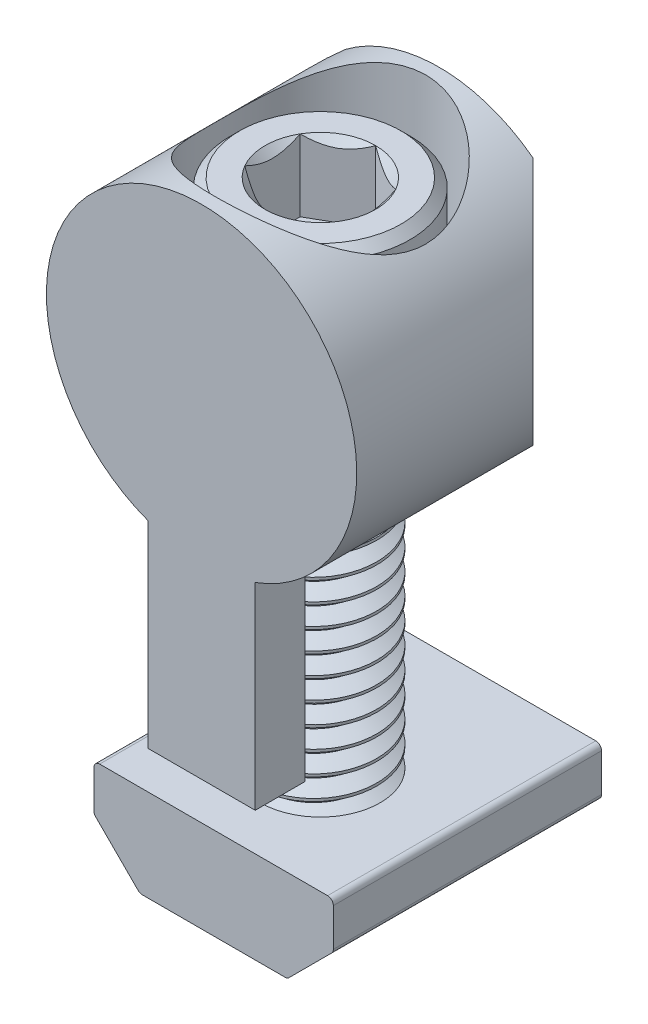
SolidWorks part; units mm, degrees
ref_plane "Front Plane" through (0, 0, 0) normal (0, 0, 1) x (1, 0, 0)
ref_plane "Top Plane" through (0, 0, 0) normal (0, 1, 0) x (1, 0, 0)
ref_plane "Right Plane" through (0, 0, 0) normal (1, 0, 0) x (0, 0, -1)
sketch "Sketch1" plane through (0, 0, 0) normal (0, 1, 0) x (1, 0, 0)
  circle A0 centre (0, 0) radius 3.9688
  point P3 (-3.9688, 0)
  dimension "D1" = 7.9375
extrude "Boss-Extrude1" add sketch "Sketch1" against normal blind 33.02
sketch "Sketch2" plane through (0, -33.02, 0) normal (0, -1, 0) x (1, 0, 0)
  circle A1 centre (0, 0) radius 3.9688
  circle A2 centre (0, 0) radius 3.9688
  point P0 (0, -3.9688)
  dimension "D1" = 0
curve "Helix/Spiral1" pitch 1.4111 height 34.4311 turns 24.4
sketch "Sketch3" plane through (0, 0, 0) normal (1, 0, 0) x (0, 0, -1)
  line L0 (4.1215, -32.9318) -> (2.8994, -33.6374) construction
  line L1 (2.8994, -33.6374) -> (4.1215, -34.3429) construction
  line L2 (4.1215, -34.3429) -> (4.1215, -32.9318) construction
  line L3 (3.0522, -33.5492) -> (3.0522, -33.7256) construction
  line L4 (3.9688, -33.02) -> (3.9688, -34.2547) construction
  line L5 (2.8994, -33.6374) -> (3.0522, -33.6374) construction
  line L6 (3.9688, -33.6374) -> (4.1215, -33.6374) construction
  line L8 (2.8994, -33.6374) -> (-3.9688, -33.6374) construction
  line L9 (3.0522, -33.5492) -> (4.0451, -32.9759)
  line L10 (3.0522, -33.5492) -> (3.0522, -33.7256)
  line L11 (3.0522, -33.7256) -> (4.0451, -34.2988)
  line L12 (4.0451, -34.2988) -> (4.0451, -32.9759)
  line L14 (-3.9688, -33.6374) -> (-3.9688, -32.2263) construction
  line L15 (-3.9688, -32.2263) -> (-3.9688, -30.8151) construction
  line L16 (-3.9688, -30.8151) -> (-3.9688, -29.404) construction
  line L17 (-3.9688, -29.404) -> (-3.9687, -27.9929) construction
  line L18 (-3.9688, 0) -> (-3.9688, -33.02) construction
  point P15 (4.0451, -33.6374)
  dimension "D1" = 1.4111
  dimension "D2" = 0.1764
sweep "Cut-Sweep1" cut profiles "Sketch3" path "Helix/Spiral1" align with end faces yes
sketch "Sketch4" plane through (0, -33.02, 0) normal (0, -1, 0) x (1, 0, 0)
  circle A0 centre (0, 0) radius 2.8994
extrude "Cut-Extrude1" cut sketch "Sketch4" against normal blind 1.4111 draft 45 flip side to cut
sketch "Sketch5" plane through (0, 0, 0) normal (0, 1, 0) x (1, 0, 0)
  circle A0 centre (0, 0) radius 5.9531
  dimension "D1" = 11.9062
extrude "Boss-Extrude2" add sketch "Sketch5" along normal blind 7.9375
sketch "Sketch6" plane through (0, 7.9375, 0) normal (0, 1, 0) x (1, 0, 0)
  line L1 (0, 3.6662) -> (-3.175, 1.8331)
  line L2 (-3.175, 1.8331) -> (-3.175, -1.8331)
  line L3 (-3.175, -1.8331) -> (0, -3.6662)
  line L4 (0, -3.6662) -> (3.175, -1.8331)
  line L5 (3.175, -1.8331) -> (3.175, 1.8331)
  line L6 (3.175, 1.8331) -> (0, 3.6662)
  circle A0 centre (0, 0) radius 3.175 construction
extrude "Cut-Extrude2" cut sketch "Sketch6" against normal blind 4.7625
sketch "Sketch7" plane through (0, 7.9375, 0) normal (0, 1, 0) x (1, 0, 0)
  circle A0 centre (0, 0) radius 3.6662
extrude "Cut-Extrude3" cut sketch "Sketch7" against normal blind 4.7625 draft 45
chamfer "Chamfer1" distance 0.5953 angle 45 1 edges at (0, 7.9375, 5.9531)
sketch "Sketch8" plane through (0, 0, 0) normal (0, 0, 1) x (1, 0, 0)
  line L0 (0, 10.3378) -> (0, -32.0802) construction
  line L1 (-3.5583, -9.6012) -> (-3.5583, -22.6822) construction
  line L2 (-3.5583, -22.6822) -> (3.5583, -22.6822) construction
  line L3 (3.5583, -22.6822) -> (3.5583, -9.6012) construction
  line L4 (4.8895, -32.0802) -> (-4.8895, -32.0802) construction
  line L5 (-4.8895, -32.0802) -> (-7.9375, -29.0322) construction
  line L6 (-7.9375, -29.0322) -> (-7.9375, -25.9842) construction
  line L7 (-7.9375, -25.9842) -> (7.9375, -25.9842) construction
  line L8 (7.9375, -29.0322) -> (7.9375, -25.9842) construction
  line L9 (4.8895, -32.0802) -> (7.9375, -29.0322) construction
  line L10 (-4.8895, -32.0802) -> (-7.9375, -32.0802) construction
  line L11 (-7.9375, -32.0802) -> (-7.9375, -29.0322) construction
  circle A0 centre (0, 0.0508) radius 10.287
  point P1 (0, -22.6822)
  dimension "D1" = 33.02
  dimension "D3" = 20.574
  dimension "D2" = 13.081
  dimension "D4" = 7.1165
  dimension "D5" = 6.096
  dimension "D6" = 15.875
  dimension "D7" = 0.0508
  dimension "D8" = 42.418
extrude "Boss-Extrude3" add sketch "Sketch8" along normal mid plane 15.748 separate body
sketch "Sketch9" plane through (0, 0, 7.874) normal (0, 0, 1) x (1, 0, 0)
  line L0 (-3.5583, -9.6012) -> (-3.5583, -22.6822) construction
  line L1 (-3.5583, -22.6822) -> (3.5583, -22.6822) construction
  line L2 (3.5583, -22.6822) -> (3.5583, -9.6012) construction
  line L3 (-3.5583, -9.6012) -> (-3.5583, -22.6822)
  line L4 (-3.5583, -22.6822) -> (3.5583, -22.6822)
  line L5 (3.5583, -22.6822) -> (3.5583, -9.6012)
  circle A0 centre (0, 0.0508) radius 10.287 construction
  arc A1 (-3.5583, -9.6012) -> (3.5583, -9.6012) centre (0, 0.0508) ccw
extrude "Boss-Extrude4" add sketch "Sketch9" against normal blind 3.302
sketch "Sketch10" plane through (0, 0, 0) normal (0, 1, 0) x (1, 0, 0)
  line L1 (-10.287, 7.874) -> (-10.287, 3.81)
  line L2 (-10.287, 3.81) -> (-6.223, 7.874)
  line L3 (10.287, 7.874) -> (-10.287, 7.874) construction
  line L4 (-6.223, 7.874) -> (-10.287, 7.874)
  line L5 (10.287, 7.874) -> (6.223, 7.874)
  line L6 (6.223, 7.874) -> (10.287, 3.81)
  line L7 (10.287, 3.81) -> (10.287, 7.874)
  dimension "D2" = 4.064
extrude "Cut-Extrude4" cut sketch "Sketch10" against normal through all and the other way through all
sketch "Sketch11" plane through (0, 0, 0) normal (0, 1, 0) x (1, 0, 0)
  circle A0 centre (0, 0) radius 6.985
  dimension "D1" = 13.97
extrude "Cut-Extrude5" cut sketch "Sketch11" along normal through all
sketch "Sketch12" plane through (0, 0, 0) normal (0, 1, 0) x (1, 0, 0)
  circle A2 centre (0, 0) radius 4.064
  dimension "D1" = 8.128
extrude "Cut-Extrude6" cut sketch "Sketch12" against normal through all
sketch "Sketch13" plane through (0, 0, 7.874) normal (0, 0, 1) x (1, 0, 0)
  line L0 (-7.9375, -29.0322) -> (-7.9375, -25.9842) construction
  line L1 (-7.9375, -25.9842) -> (7.9375, -25.9842) construction
  line L2 (7.9375, -29.0322) -> (7.9375, -25.9842) construction
  line L3 (4.8895, -32.0802) -> (7.9375, -29.0322) construction
  line L4 (-4.8895, -32.0802) -> (-7.9375, -29.0322) construction
  line L5 (-7.9375, -29.0322) -> (-7.9375, -25.9842)
  line L6 (-7.9375, -25.9842) -> (7.9375, -25.9842)
  line L7 (7.9375, -29.0322) -> (7.9375, -25.9842)
  line L8 (4.8895, -32.0802) -> (7.9375, -29.0322)
  line L9 (-4.8895, -32.0802) -> (-7.9375, -29.0322)
  line L10 (4.8895, -32.0802) -> (-4.8895, -32.0802) construction
  line L11 (4.8895, -32.0802) -> (-4.8895, -32.0802)
extrude "Boss-Extrude5" add sketch "Sketch13" against normal blind 17.78 from offset 0.8001 separate body offset against normal yes
sketch "Sketch14" plane through (0, -25.9842, 0) normal (0, 1, 0) x (1, 0, 0)
  circle A1 centre (0, 0) radius 3.9688
  circle A2 centre (0, 0) radius 3.9688
  dimension "D1" = 0
extrude "Cut-Extrude7" cut sketch "Sketch14" against normal through all
fillet "Fillet1" radius 0.381 6 edges at (7.9375, -29.0322, -1.8161) (7.9375, -25.9842, -1.8161) (-7.9375, -29.0322, -1.8161) (-7.9375, -25.9842, -1.8161) (4.8895, -32.0802, -1.8161) (-4.8895, -32.0802, -1.8161)
equation "\"D3@Helix/Spiral1\" = \"D4@Helix/Spiral1\" + \"D1@Boss-Extrude1\""
equation "\"D1@Sketch3\" = \"D4@Helix/Spiral1\""
equation "\"D2@Sketch3\" = \"D1@Sketch3\" / 8"
equation "\"D1@Cut-Extrude1\" = \"D4@Helix/Spiral1\""
equation "\"D1@Cut-Extrude2\" = \"D1@Sketch6\" * 3/4"
equation "\"D1@Cut-Extrude3\" = \"D1@Cut-Extrude2\""
equation "\"D1@Chamfer1\" = \"D1@Sketch5\" * 0.05"
